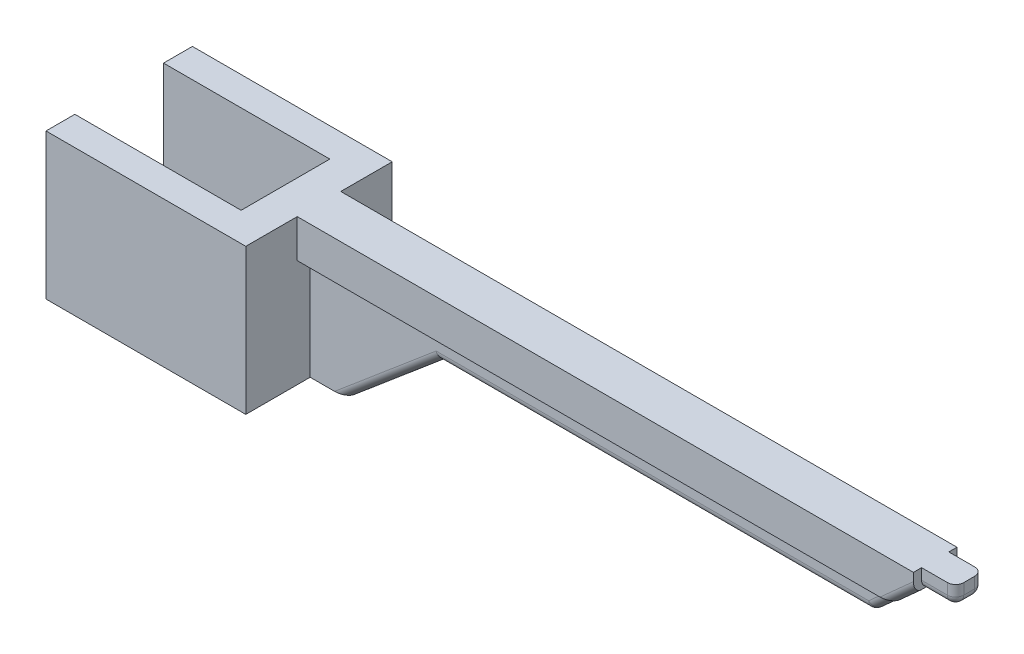
SolidWorks part; units mm, degrees
ref_plane "Front Plane" through (0, 0, 0) normal (0, 0, 1) x (1, 0, 0)
ref_plane "Top Plane" through (0, 0, 0) normal (0, 1, 0) x (1, 0, 0)
ref_plane "Right Plane" through (0, 0, 0) normal (1, 0, 0) x (0, 0, -1)
sketch "Sketch1" plane through (0, 0, 0) normal (0, 1, 0) x (1, 0, 0)
  line L1 (-30, 3.75) -> (30, 3.75)
  line L2 (-30, 3.75) -> (-30, -3.75)
  line L3 (-30, -3.75) -> (30, -3.75)
  line L4 (30, 3.75) -> (30, -3.75)
  line L5 (-30, 3.75) -> (30, -3.75) construction
  line L6 (-30, -3.75) -> (30, 3.75) construction
  point P1 (0, 0)
  dimension "D1" = 60
  dimension "D2" = 7.5
extrude "Boss-Extrude1" add sketch "Sketch1" along normal blind 13
sketch "Sketch3" plane through (0, 13, 0) normal (0, 1, 0) x (1, 0, 0)
  line L0 (-30, 2.5) -> (-18, 2.5)
  line L1 (-30, 3.75) -> (-30, -3.75) construction
  line L2 (0, 0) -> (-30, 0) construction
  line L3 (-18, 2.5) -> (-18, -2.5)
  line L4 (-30, -2.5) -> (-18, -2.5)
  line L5 (-30, 2.5) -> (-30, -2.5)
  dimension "D1" = 2.5
  dimension "D2" = 12
extrude "Cut-Extrude1" cut sketch "Sketch3" against normal blind 10.5
sketch "Sketch4" plane through (0, 2.5, 0) normal (0, 1, 0) x (1, 0, 0)
  line L0 (-21, 0) -> (-26.7, 0)
  line L2 (-18, 0) -> (-21, 0)
  line L3 (-18, -2.5) -> (-18, 2.5) construction
  circle A0 centre (-21, 0) radius 1
  circle A1 centre (-26.7, 0) radius 1
  dimension "D2" = 2
  dimension "D4" = 2
  dimension "D1" = 3
  dimension "D3" = 5.7
extrude "Cut-Extrude2" cut sketch "Sketch4" against normal blind 10 contours A1 | L2 A0 L0 | L0 A0 L2 | A0 region at (-21, 2.5, 0.4244) region at (-21, 2.5, -0.4244) region at (-27.6717, 2.5, 0)
sketch "Sketch9" plane through (0, 0, 0) normal (0, -1, 0) x (1, 0, 0)
  line L0 (30, 0) -> (-18, 0) construction
  line L1 (30, 3.75) -> (30, -3.75) construction
  line L2 (30, 1.6) -> (-15.2776, 1.6)
  line L6 (-15.2776, 1.6) -> (-15.2776, 3.75)
  line L7 (-30, 3.75) -> (30, 3.75) construction
  line L8 (-15.2776, 3.75) -> (30, 3.75)
  line L9 (30, 3.75) -> (30, 1.6)
  line L10 (30, -3.75) -> (30, -1.6)
  line L11 (-15.2776, -3.75) -> (30, -3.75)
  line L12 (-15.2776, -1.6) -> (-15.2776, -3.75)
  line L13 (30, -1.6) -> (-15.2776, -1.6)
  dimension "D1" = 48
  dimension "D2" = 1.6
extrude "Cut-Extrude8" cut sketch "Sketch9" against normal blind 15
sketch "Sketch13" plane through (0, 0, 0) normal (0, -1, 0) x (1, 0, 0)
  line L0 (30, 1.6) -> (-15.2776, 1.6)
  line L1 (-15.2776, 1.6) -> (-15.2776, -1.6)
  line L2 (-15.2776, -1.6) -> (30, -1.6)
  line L3 (30, -1.6) -> (30, 1.6)
extrude "Cut-Extrude10" cut sketch "Sketch13" against normal blind 8
sketch "Sketch14" plane through (0, 8, 0) normal (0, -1, 0) x (1, 0, 0)
  line L0 (30, 0) -> (-15.2776, 0) construction
  line L1 (30, -1.6) -> (30, 1.6) construction
  line L2 (-15.2776, 1.6) -> (-15.2776, -1.6) construction
  line L3 (30, 0.65) -> (-15.2776, 0.65)
  line L4 (-15.2776, 3.75) -> (-15.2776, -3.75) construction
  line L5 (-15.2776, 0.65) -> (-15.2776, 1.6)
  line L6 (-15.2776, 1.6) -> (30, 1.6)
  line L7 (30, 1.6) -> (30, 0.65)
  line L8 (30, -1.6) -> (30, -0.65)
  line L9 (-15.2776, -1.6) -> (30, -1.6)
  line L10 (-15.2776, -0.65) -> (-15.2776, -1.6)
  line L11 (30, -0.65) -> (-15.2776, -0.65)
  dimension "D1" = 0.65
extrude "Cut-Extrude11" cut sketch "Sketch14" against normal blind 2.2
sketch "Sketch16" plane through (0, 0, 0) normal (0, 0, 1) x (1, 0, 0)
  line L0 (-5.8022, 8) -> (-15.2776, 0)
  line L1 (-15.2776, 8) -> (30, 8) construction
rib "Rib10" sketch "Sketch16" sketch "Sketch16" thickness 1.3 extrusion direction parallel to sketch draft on no parameters "D1"=1.3
sketch "Sketch17" plane through (0, 0, -1.6) normal (0, 0, -1) x (-1, 0, 0)
  line L0 (-30, 11.6) -> (-25.9962, 8)
  line L1 (-30, 13) -> (-30, 10.2) construction
  line L2 (-30, 8) -> (5.8022, 8) construction
  line L3 (-25.9962, 8) -> (-30, 8)
  line L4 (-30, 8) -> (-30, 11.6)
extrude "Cut-Extrude12" cut sketch "Sketch17" against normal blind 20
sketch "Sketch19" plane through (30, 0, 0) normal (1, 0, 0) x (0, 0, -1)
  line L0 (0, 13) -> (0, 11.6) construction
  line L1 (-1.6, 13) -> (1.6, 13) construction
  line L2 (-1.6, 11.6) -> (1.6, 11.6) construction
  line L3 (1, 13) -> (-1, 13)
  line L4 (-1, 13) -> (-1, 11.6)
  line L5 (-1, 11.6) -> (1, 11.6)
  line L6 (1, 13) -> (1, 11.6)
  dimension "D1" = 1
extrude "Boss-Extrude2" add sketch "Sketch19" along normal blind 2.5
fillet "Fillet1" radius 0.6 1 edges at (32.5, 12.3, 1)
fillet "Fillet2" radius 0.6 1 edges at (32.5, 12.3, -1)
fillet "Fillet3" radius 0.6 5 edges at (30.95, 11.6, 1) (32.3243, 11.6, 0.8243) (30.95, 11.6, -1) (32.3243, 11.6, -0.8243) (32.5, 11.6, 0)
fillet "Fillet4" radius 0.6 6 edges at (10.097, 8, 0.65) (10.097, 8, -0.65) (-10.5399, 4, 0.65) (-10.5399, 4, -0.65) (-22.6388, 0, -3.75) (-22.6388, 0, 3.75)
fillet "Fillet5" radius 0.6 7 edges at (27.5532, 9.4, 0.65) (26.1916, 8.1757, 0.4743) (25.9962, 8, 0) (26.1916, 8.1757, -0.4743) (27.5532, 9.4, -0.65) (29.2215, 10.9, -1.6) (29.2215, 10.9, 1.6)
sketch "Sketch20" plane through (0, 2.5, 0) normal (0, 1, 0) x (1, 0, 0)
  line L0 (-30, 2.5) -> (-18, 2.5)
  line L1 (-18, 2.5) -> (-18, -2.5)
  line L2 (-18, -2.5) -> (-18, 2.5) construction
  line L3 (-18, -2.5) -> (-30, -2.5)
  line L4 (-30, -2.5) -> (-30, 2.5)
extrude "Boss-Extrude3" add sketch "Sketch20" along normal blind 3
sketch "Sketch22" plane through (0, 5.5, 0) normal (0, 1, 0) x (1, 0, 0)
  line L0 (-30, 2.5) -> (-18, 2.5)
  line L1 (-18, 2.5) -> (-18, -2.5)
  line L2 (-18, -2.5) -> (-30, -2.5)
  line L3 (-30, -2.5) -> (-30, 2.5)
extrude "Cut-Extrude13" cut sketch "Sketch22" against normal blind 1.95
sketch "Sketch23" plane through (0, 0, 0) normal (0, -1, 0) x (1, 0, 0)
  circle A0 centre (-26.7, 0) radius 1
  circle A1 centre (-21, 0) radius 1
extrude "Cut-Extrude14" cut sketch "Sketch23" against normal blind 10
sketch "Sketch24" plane through (0, 0, 3.75) normal (0, 0, 1) x (1, 0, 0)
  line L0 (-30, 2.3003) -> (-15.2776, 2.3003)
  line L1 (-30, 13) -> (-30, 0.6) construction
  line L2 (-15.2776, 10.2) -> (-15.2776, 0.7853) construction
  line L3 (-15.2776, 2.3003) -> (-15.2776, 0)
  line L4 (-15.2776, 0) -> (-30, 0)
  line L5 (-30, 0) -> (-30, 2.3003)
extrude "Cut-Extrude15" cut sketch "Sketch24" against normal blind 10
sketch "Sketch25" plane through (-15.2776, 0, 0) normal (-1, 0, 0) x (0, 0, 1)
  line L0 (-0.65, 2.3003) -> (-0.65, -0.2556)
  line L1 (-0.65, -0.2556) -> (0.65, -0.2556)
  line L2 (0.65, -0.2556) -> (0.65, 2.3003)
  line L3 (0.65, 2.3003) -> (0.65, 0.7853) construction
  line L4 (-3.75, 2.3003) -> (3.75, 2.3003) construction
  line L5 (0.65, 2.3003) -> (-0.65, 2.3003)
extrude "Cut-Extrude16" cut sketch "Sketch25" against normal blind 10
scale "Scale1" scale about centroid uniform scaling yes scale factor 1.6
scale "Scale3" scale about centroid uniform scaling yes scale factor 0.8
scale "Scale4" scale about centroid uniform scaling yes scale factor 0.958904
sketch "Sketch34" plane through (0, 2.3482, 0) normal (0, 1, 0) x (1, 0, 0)
  line L3 (-19.8893, -4) -> (-19.8893, 4)
  line L4 (-19.8893, 4) -> (-34.9359, 4)
  line L5 (-34.9359, 4.6027) -> (-34.9359, 3.0685) construction
  line L6 (-34.9359, 4) -> (-34.9359, -4)
  line L9 (-19.8893, -4) -> (-34.9359, -4)
extrude "Cut-Extrude20" cut sketch "Sketch34" along normal blind 15
sketch "Sketch36" plane through (-34.9359, 0, 0) normal (-1, 0, 0) x (0, 0, 1)
  line L0 (-4, 13.9471) -> (-4.6027, 13.9471)
  line L1 (-4.6027, 13.9471) -> (-4.6027, 0.8144)
  line L2 (-4.6027, 0.8144) -> (4.6027, 0.8144)
  line L3 (4.6027, 0.8144) -> (4.6027, 13.9471)
  line L4 (4.6027, 13.9471) -> (4, 13.9471)
  line L5 (4, 13.9471) -> (4, 2.3482)
  line L6 (4, 2.3482) -> (-4, 2.3482)
  line L7 (-4, 2.3482) -> (-4, 13.9471)
extrude "Cut-Extrude21" cut sketch "Sketch36" against normal blind 0.5
sketch "Sketch38" plane through (0, 0, -4.6027) normal (0, 0, -1) x (-1, 0, 0)
  line L0 (16.8656, 13.9471) -> (34.4359, 13.9471)
  line L1 (34.4359, 13.9471) -> (34.4359, 0.8144)
  line L2 (34.4359, 0.8144) -> (16.8656, 0.8144)
  line L3 (16.8656, 0.8144) -> (16.8656, 13.9471)
extrude "Boss-Extrude4" add sketch "Sketch38" along normal blind 2
sketch "Sketch39" plane through (0, 0, 4.6027) normal (0, 0, 1) x (1, 0, 0)
  line L0 (-34.4359, 13.9471) -> (-16.8656, 13.9471)
  line L1 (-16.8656, 13.9471) -> (-16.8656, 0.8144)
  line L2 (-16.8656, 0.8144) -> (-34.4359, 0.8144)
  line L3 (-34.4359, 0.8144) -> (-34.4359, 13.9471)
extrude "Boss-Extrude5" add sketch "Sketch39" along normal blind 2
sketch "Sketch40" plane through (0, 2.3482, 0) normal (0, 1, 0) x (1, 0, 0)
  line L0 (-34.4359, 4) -> (-19.8893, 4)
sketch "Sketch42" plane through (0, 2.3482, 0) normal (0, 1, 0) x (1, 0, 0)
  line L0 (-19.8893, 0) -> (-23.8893, 0)
  line L1 (-19.8893, 4) -> (-19.8893, -4) construction
  line L2 (-23.8893, 0) -> (-30.8855, 0)
  line L3 (-30.8855, 0) -> (-34.4359, 0)
  line L4 (-34.4359, -4) -> (-34.4359, 4) construction
  dimension "D1" = 6.9962
  dimension "D2" = 3.5504
sketch "Sketch43" plane through (-34.4359, 0, 0) normal (-1, 0, 0) x (0, 0, 1)
  line L0 (-6.6027, 13.9471) -> (-6.6027, 0.8144)
  line L1 (-6.6027, 0.8144) -> (6.6027, 0.8144)
  line L2 (6.6027, 0.8144) -> (6.6027, 13.9471)
  line L3 (6.6027, 13.9471) -> (4, 13.9471)
  line L4 (4, 13.9471) -> (4, 2.3482)
  line L5 (4, 2.3482) -> (-4, 2.3482)
  line L6 (-4, 2.3482) -> (-4, 13.9471)
  line L7 (-4, 13.9471) -> (-6.6027, 13.9471)
extrude "Boss-Extrude6" add sketch "Sketch43" along normal blind 0.45
